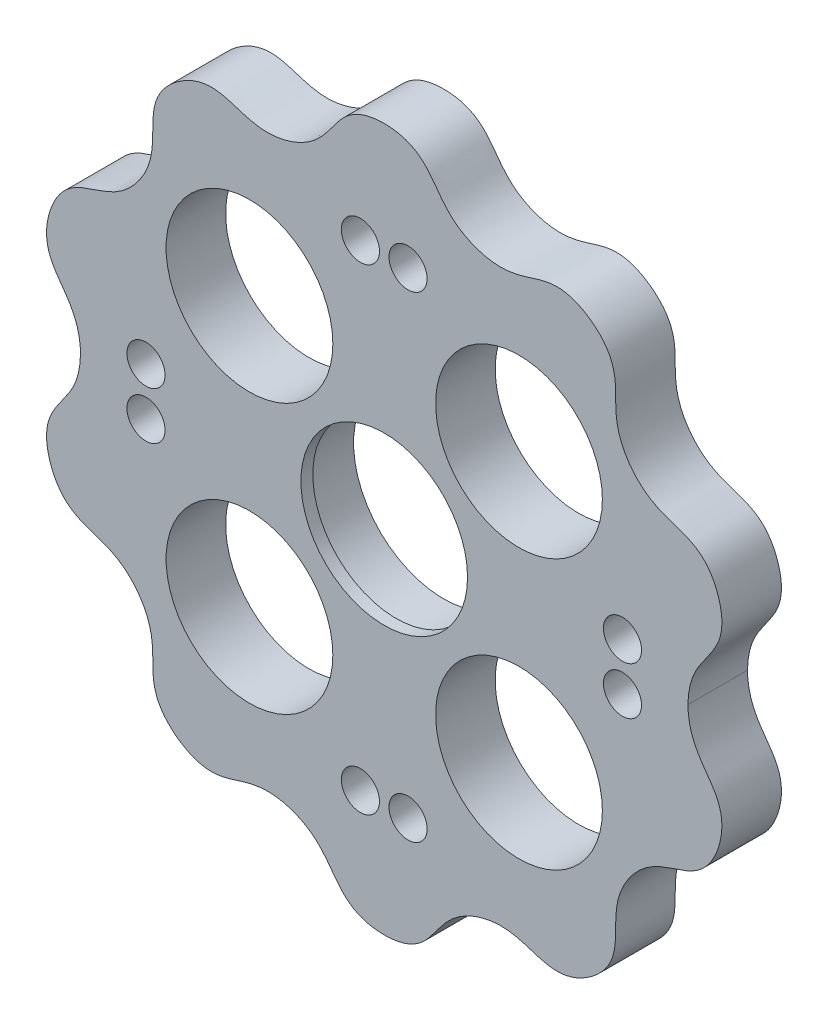
SolidWorks part; units mm, degrees
ref_plane "Front Plane" through (0, 0, 0) normal (0, 0, 1) x (1, 0, 0)
ref_plane "Top Plane" through (0, 0, 0) normal (0, 1, 0) x (1, 0, 0)
ref_plane "Right Plane" through (0, 0, 0) normal (1, 0, 0) x (0, 0, -1)
ref_plane "Plane1" through (0, 0, 4) normal (0, 0, 1) x (1, 0, 0)
sketch "Sketch3" plane through (0, 0, 4) normal (0, 0, 1) x (1, 0, 0)
  circle A0 centre (2, 0) radius 7.5
  spline S0 degree 5 poles (-23.5, 0) (-23.5, -0.6619) (-23.5985, -1.4561) (-23.8874, -2.4734) (-24.5265, -3.4803) (-25.3239, -4.5428) (-25.7599, -5.1922) (-26.203, -6.107) (-26.3992, -6.9747) (-26.3685, -8.1757) (-26.0322, -9.4106) (-25.4671, -10.5179) (-24.8895, -11.2256) (-23.9802, -11.9083) (-23.1576, -12.2723) (-21.7572, -12.687) (-20.1242, -13.2676) (-18.7699, -14.5833) (-17.7259, -16.1905) (-17.3933, -18.0022) (-17.4393, -19.3418) (-17.4288, -20.3924) (-17.2271, -21.518) (-16.8759, -22.3353) (-16.145, -23.2889) (-15.1471, -24.0902) (-14.0391, -24.6539) (-13.1558, -24.8869) (-12.0189, -24.9048) (-11.1394, -24.7158) (-9.7628, -24.2281) (-8.1004, -23.738) (-6.2314, -24.0063) (-4.442, -24.693) (-3.1081, -25.9632) (-2.3579, -27.074) (-1.7319, -27.9177) (-0.9071, -28.7098) (-0.1425, -29.1646) (1.0093, -29.5065) (2.2876, -29.5682) (3.5153, -29.373) (4.3668, -29.0423) (5.2971, -28.3885) (5.8976, -27.7187) (6.7246, -26.515) (7.7814, -25.1413) (9.4513, -24.2598) (11.3025, -23.7636) (13.1282, -24.0071) (14.3881, -24.4648) (15.3905, -24.7795) (16.5233, -24.9355) (17.4092, -24.854) (18.5419, -24.4536) (19.6124, -23.7522) (20.4909, -22.8726) (20.9855, -22.1045) (21.3538, -21.0288) (21.4458, -20.1339) (21.4074, -18.674) (21.455, -16.9415) (22.2878, -15.2469) (23.4937, -13.7573) (25.1139, -12.8812) (26.4022, -12.5109) (27.3981, -12.1763) (28.4063, -11.6367) (29.0751, -11.05) (29.7562, -10.0602) (30.2099, -8.8636) (30.4037, -7.6356) (30.3523, -6.7236) (30.018, -5.6368) (29.5664, -4.8587) (28.6772, -3.7002) (27.9235, -2.6005) (27.5985, -1.4561) (27.5, -0.6619) (27.5, 0) knots 0.5 0.5 0.5 0.5 0.5 0.5 0.516667 0.52 0.526667 0.53 0.533333 0.536667 0.546667 0.55 0.56 0.563333 0.566667 0.57 0.58 0.583333 0.6 0.61 0.616667 0.626667 0.63 0.633333 0.636667 0.646667 0.65 0.66 0.663333 0.666667 0.67 0.68 0.683333 0.7 0.71 0.716667 0.726667 0.73 0.733333 0.736667 0.746667 0.75 0.76 0.763333 0.766667 0.77 0.78 0.783333 0.8 0.81 0.816667 0.826667 0.83 0.833333 0.836667 0.846667 0.85 0.86 0.863333 0.866667 0.87 0.88 0.883333 0.9 0.91 0.916667 0.926667 0.93 0.933333 0.936667 0.946667 0.95 0.96 0.963333 0.966667 0.97 0.98 0.983333 1 1 1 1 1 1 weights 1 1 1 1 1 1 1 1 1 1 1 1 1 1 1 1 1 1 1 1 1 1 1 1 1 1 1 1 1 1 1 1 1 1 1 1 1 1 1 1 1 1 1 1 1 1 1 1 1 1 1 1 1 1 1 1 1 1 1 1 1 1 1 1 1 1 1 1 1 1 1 1 1 1 1 1 1 1 1 1
  spline S1 degree 5 poles (27.5, 0) (27.5, 0.6619) (27.5985, 1.4561) (27.8874, 2.4734) (28.5265, 3.4803) (29.3239, 4.5428) (29.7599, 5.1922) (30.203, 6.107) (30.3992, 6.9747) (30.3685, 8.1757) (30.0322, 9.4106) (29.4671, 10.5179) (28.8895, 11.2256) (27.9802, 11.9083) (27.1576, 12.2723) (25.7572, 12.687) (24.1242, 13.2676) (22.7699, 14.5833) (21.7259, 16.1905) (21.3933, 18.0022) (21.4393, 19.3418) (21.4288, 20.3924) (21.2271, 21.518) (20.8759, 22.3353) (20.145, 23.2889) (19.1471, 24.0902) (18.0391, 24.6539) (17.1558, 24.8869) (16.0189, 24.9048) (15.1394, 24.7158) (13.7628, 24.2281) (12.1004, 23.738) (10.2314, 24.0063) (8.442, 24.693) (7.1081, 25.9632) (6.3579, 27.074) (5.7319, 27.9177) (4.9071, 28.7098) (4.1425, 29.1646) (2.9907, 29.5065) (1.7124, 29.5682) (0.4847, 29.373) (-0.3668, 29.0423) (-1.2971, 28.3885) (-1.8976, 27.7187) (-2.7246, 26.515) (-3.7814, 25.1413) (-5.4513, 24.2598) (-7.3025, 23.7636) (-9.1282, 24.0071) (-10.3881, 24.4648) (-11.3905, 24.7795) (-12.5233, 24.9355) (-13.4092, 24.854) (-14.5419, 24.4536) (-15.6124, 23.7522) (-16.4909, 22.8726) (-16.9855, 22.1045) (-17.3538, 21.0288) (-17.4458, 20.1339) (-17.4074, 18.674) (-17.455, 16.9415) (-18.2878, 15.2469) (-19.4937, 13.7573) (-21.1139, 12.8812) (-22.4022, 12.5109) (-23.3981, 12.1763) (-24.4063, 11.6367) (-25.0751, 11.05) (-25.7562, 10.0602) (-26.2099, 8.8636) (-26.4037, 7.6356) (-26.3523, 6.7236) (-26.018, 5.6368) (-25.5664, 4.8587) (-24.6772, 3.7002) (-23.9235, 2.6005) (-23.5985, 1.4561) (-23.5, 0.6619) (-23.5, 0) knots 0 0 0 0 0 0 0.016667 0.02 0.026667 0.03 0.033333 0.036667 0.046667 0.05 0.06 0.063333 0.066667 0.07 0.08 0.083333 0.1 0.11 0.116667 0.126667 0.13 0.133333 0.136667 0.146667 0.15 0.16 0.163333 0.166667 0.17 0.18 0.183333 0.2 0.21 0.216667 0.226667 0.23 0.233333 0.236667 0.246667 0.25 0.26 0.263333 0.266667 0.27 0.28 0.283333 0.3 0.31 0.316667 0.326667 0.33 0.333333 0.336667 0.346667 0.35 0.36 0.363333 0.366667 0.37 0.38 0.383333 0.4 0.41 0.416667 0.426667 0.43 0.433333 0.436667 0.446667 0.45 0.46 0.463333 0.466667 0.47 0.48 0.483333 0.5 0.5 0.5 0.5 0.5 0.5 weights 1 1 1 1 1 1 1 1 1 1 1 1 1 1 1 1 1 1 1 1 1 1 1 1 1 1 1 1 1 1 1 1 1 1 1 1 1 1 1 1 1 1 1 1 1 1 1 1 1 1 1 1 1 1 1 1 1 1 1 1 1 1 1 1 1 1 1 1 1 1 1 1 1 1 1 1 1 1 1 1
extrude "CYC Disk" add sketch "Sketch3" along normal blind 5
sketch "Sketch6" plane through (0, 0, 9) normal (0, 0, 1) x (1, 0, 0)
  line L0 (0, 0) -> (2, 0) construction
  circle A1 centre (2, 0) radius 7.575
  dimension "D2" = 15.15
  dimension "D1" = 2
extrude "Cam Bearing" cut sketch "Sketch6" against normal through all
sketch "Sketch7" plane through (0, 0, 9) normal (0, 0, 1) x (1, 0, 0)
  line L0 (2, 0) -> (18, 0) construction
  line L1 (2, 0) -> (13.3137, 11.3137) construction
  circle A0 centre (2, 0) radius 16 construction
  circle A1 centre (13.3137, 11.3137) radius 7
  circle A2 centre (13.3137, -11.3137) radius 7
  circle A3 centre (-9.3137, -11.3137) radius 7
  circle A4 centre (-9.3137, 11.3137) radius 7
  point P15 (2, 0)
  dimension "D1" = 32
  dimension "D2" = 45
  dimension "D3" = 14
  dimension "D4" = 4
extrude "Output Holes" cut sketch "Sketch7" against normal through all
sketch "Sketch8" plane through (0, 0, 9) normal (0, 0, 1) x (1, 0, 0)
  circle A0 centre (2, 0) radius 6.9953
  circle A1 centre (2, 0) radius 7.575
extrude "Cam Bearing Retainer" add sketch "Sketch8" against normal blind 1
sketch "Sketch9" plane through (0, 0, 9) normal (0, 0, 1) x (1, 0, 0)
  line L0 (2, 0) -> (2, 20) construction
  line L2 (4, 20) -> (2, 20)
  line L3 (2, 20) -> (0, 20)
  circle A2 centre (0, 20) radius 1.6
  circle A3 centre (4, 20) radius 1.6
  circle A4 centre (22, -2) radius 1.6
  circle A5 centre (22, 2) radius 1.6
  circle A6 centre (0, -20) radius 1.6
  circle A7 centre (4, -20) radius 1.6
  circle A8 centre (-18, 2) radius 1.6
  circle A9 centre (-18, -2) radius 1.6
  point P8 (2, 0)
  point P23 (2, 0)
  dimension "D3" = 2
  dimension "D4" = 3.2
  dimension "D5" = 3.2
  dimension "D6" = 4
  dimension "D1" = 2
  dimension "D2" = 20
extrude "Positioning Holes" cut sketch "Sketch9" against normal through all contours A3 | A5 | A4 | A7 | A6 | A9 | A8 | A2 region at (4, 21.5547, 9) region at (22, -2, 9) region at (22, 2, 9) region at (0, -20, 9) region at (4, -20, 9) region at (-18, 2, 9) region at (-18, -2, 9)
equation "\"CamBearingOut\"=15.15"
equation "\"D2@Sketch6\"=\"CamBearingOut\""
equation "\"RingPinShaft\"= 5"
equation "\"CenterBearingOut\"=32"
equation "\"RingPostIn\"=5"
